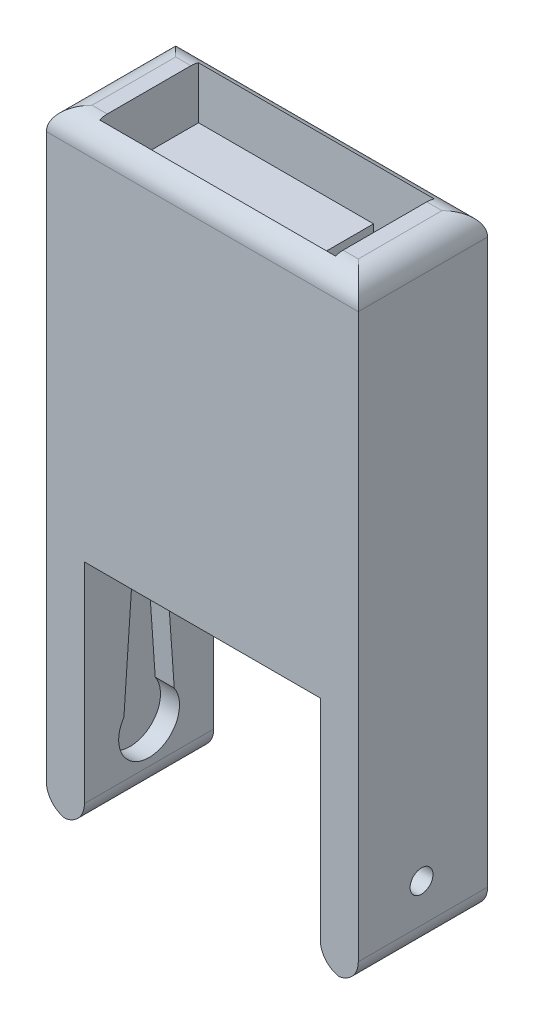
SolidWorks part; units mm, degrees
material "PLA - 20%"
ref_plane "Front Plane" through (0, 0, 0) normal (0, 0, 1) x (1, 0, 0)
ref_plane "Top Plane" through (0, 0, 0) normal (0, 1, 0) x (1, 0, 0)
ref_plane "Right Plane" through (0, 0, 0) normal (1, 0, 0) x (0, 0, -1)
sketch "Sketch1" plane through (0, 0, 0) normal (0, 1, 0) x (1, 0, 0)
  line L1 (0, 0) -> (5, 0)
  line L2 (0, 0) -> (0, -17)
  line L3 (0, -17) -> (5, -17)
  line L4 (5, 0) -> (5, -17)
  line L5 (36, 0) -> (41, 0)
  line L6 (36, 0) -> (36, -17)
  line L7 (36, -17) -> (41, -17)
  line L8 (41, 0) -> (41, -17)
  dimension "D1" = 5
  dimension "D2" = 5
  dimension "D3" = 31
  dimension "D4" = 17
  dimension "D5" = 17
extrude "Boss-Extrude1" add sketch "Sketch1" along normal blind 80
sketch "Sketch2" plane through (5, 0, 0) normal (1, 0, 0) x (0, 0, -1)
  line L0 (-11.8072, 10.25) -> (-10.75, 25.2678)
  line L1 (-11.8072, 10.25) -> (-11.8072, 5.75)
  line L2 (-17, 0) -> (0, 0) construction
  line L3 (-5.1928, 5.75) -> (-5.1928, 10.25)
  line L4 (-5.1928, 10.25) -> (-6.25, 25.2678)
  circle A0 centre (-8.5, 8) radius 4
  arc A1 (-10.75, 25.2678) -> (-6.25, 25.2678) centre (-8.5, 25.2678) cw
  point P6 (-8.5, 0)
  dimension "D1" = 8
  dimension "D3" = 2.25
  dimension "D2" = 4.5
  dimension "D4" = 4.5
  dimension "D5" = 8
extrude "Cut-Extrude1" cut sketch "Sketch2" against normal blind 2.5 contours A1 L0 A0 L4 | L3 A0 L1 | L1 A0 | L3 A0 region at (5, 8, 8.5) region at (5, 18.7534, 8.5) region at (5, 8, 12.0865) region at (5, 8, 4.9135)
sketch "Sketch4" plane through (36, 0, 0) normal (-1, 0, 0) x (0, 0, 1)
  line L0 (0, 80) -> (0, 0) construction
  line L1 (2, 73) -> (15, 73)
  line L2 (0, 72) -> (0, 68)
  line L3 (0, 68) -> (17, 68)
  line L4 (17, 72) -> (17, 68)
  line L5 (17, 80) -> (17, 0) construction
  line L6 (0, 80) -> (17, 80) construction
  line L8 (0, 80) -> (2, 80)
  line L9 (0, 80) -> (0, 72)
  line L11 (2, 80) -> (2, 73)
  line L12 (17, 80) -> (15, 80)
  line L13 (17, 80) -> (17, 72)
  line L15 (15, 80) -> (15, 73)
  dimension "D1" = 7
  dimension "D2" = 5
  dimension "D3" = 13
  dimension "D4" = 2
extrude "Boss-Extrude2" add sketch "Sketch4" along normal up to next
sketch "Sketch5" plane through (0, 73, 0) normal (0, 1, 0) x (1, 0, 0)
  line L0 (5, -15) -> (36, -15) construction
  line L1 (31, -15) -> (28, -15)
  line L2 (31, -15) -> (31, -2)
  line L3 (31, -2) -> (28, -2)
  line L4 (28, -15) -> (28, -2)
  line L5 (5, -2) -> (36, -2) construction
  line L6 (36, -15) -> (36, -2) construction
  dimension "D1" = 5
  dimension "D2" = 3
extrude "Cut-Extrude2" cut sketch "Sketch5" against normal up to next (5 mm away)
fillet "Fillet1" radius 3 5 edges at (36, 0, 8.5) (41, 0, 8.5) (41, 80, 8.5) (23, 80, 17) (23, 80, 0)
fillet "Fillet2" radius 3 5 edges at (0, 0, 8.5) (5, 0, 8.5) (2.5, 80, 17) (0, 80, 8.5) (2.5, 80, 0)
sketch "Sketch6" plane through (36, 0, 0) normal (-1, 0, 0) x (0, 0, 1)
  line L0 (0, 0.042) -> (17, 0.042) construction
  circle A0 centre (8.6864, 8.042) radius 1.5
  point P2 (8.5, 0.042)
  dimension "D2" = 3
  dimension "D1" = 8
extrude "Cut-Extrude3" cut sketch "Sketch6" against normal through all
sketch "Sketch7" plane through (5, 0, 0) normal (1, 0, 0) x (0, 0, -1)
  line L0 (0, 77) -> (0, 3) construction
  line L1 (-17, 68) -> (0, 68)
  line L2 (-17, 68) -> (-17, 30.5178)
  line L3 (-17, 30.5178) -> (0, 30.5178)
  line L4 (0, 68) -> (0, 30.5178)
  arc A0 (-6.25, 25.2678) -> (-10.75, 25.2678) centre (-8.5, 25.2678) ccw construction
  point P10 (-8.5, 27.5178)
  dimension "D1" = 3
extrude "Boss-Extrude3" add sketch "Sketch7" along normal up to next
